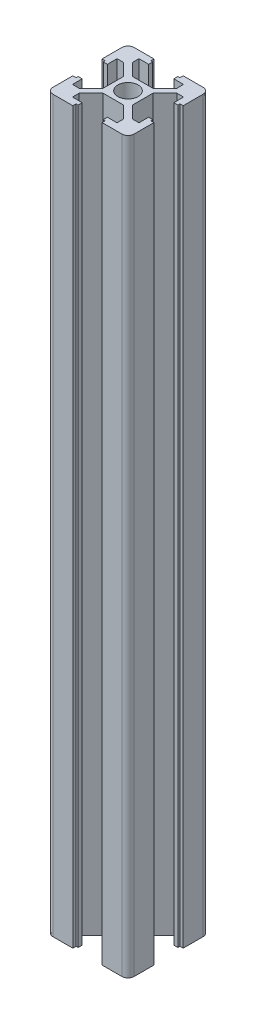
SolidWorks part; units mm, degrees
ref_plane "前视基准面" through (0, 0, 0) normal (0, 0, 1) x (1, 0, 0)
ref_plane "上视基准面" through (0, 0, 0) normal (0, 1, 0) x (1, 0, 0)
ref_plane "右视基准面" through (0, 0, 0) normal (1, 0, 0) x (0, 0, -1)
other "Configuration Table"
sketch "草图1" plane through (0, 0, 0) normal (0, 1, 0) x (1, 0, 0)
  line L0 (-4.4156, 1.3346) -> (-4.4156, 4.4346) construction
  line L1 (-4.4156, 3.874) -> (-4.4156, -1.2047)
  line L2 (1.7237, 4.9346) -> (-3.3549, 4.9346)
  line L3 (2.7844, -1.2047) -> (2.7844, 3.874)
  line L4 (-3.3549, -2.2654) -> (1.7237, -2.2654)
  line L5 (-10.8156, 1.3346) -> (9.1844, 1.3346) construction
  line L6 (-0.8156, 11.3346) -> (-0.8156, -8.6654) construction
  line L7 (-10.8156, 11.3346) -> (-0.8156, 1.3346) construction
  line L8 (-10.8156, 4.9346) -> (-4.4156, 4.9346) construction
  line L9 (-10.0156, 4.4346) -> (-3.9156, 4.4346) construction
  line L10 (-9.0156, 6.8346) -> (-6.3156, 6.8346) construction
  line L11 (-7.3763, 6.8346) -> (-4.4156, 3.874) construction
  line L12 (-10.8156, 9.8346) -> (-10.8156, 4.9346)
  line L13 (-10.8156, 4.9346) -> (-10.0156, 4.9346)
  line L14 (-10.0156, 4.9346) -> (-10.0156, 4.4346)
  line L15 (-10.0156, 4.4346) -> (-9.0156, 4.4346)
  line L16 (-9.0156, 4.4346) -> (-9.0156, 6.8346)
  line L17 (-9.0156, 6.8346) -> (-7.3763, 6.8346)
  line L18 (-7.3763, 6.8346) -> (-4.4156, 3.874)
  line L19 (-3.9156, 10.5346) -> (-3.9156, 9.5346)
  line L20 (-4.4156, 10.5346) -> (-3.9156, 10.5346)
  line L21 (-4.4156, 11.3346) -> (-4.4156, 10.5346)
  line L22 (-9.3156, 11.3346) -> (-4.4156, 11.3346)
  line L23 (-3.9156, 9.5346) -> (-6.3156, 9.5346)
  line L24 (-6.3156, 9.5346) -> (-6.3156, 7.8953)
  line L25 (-6.3156, 7.8953) -> (-3.3549, 4.9346)
  line L26 (9.1844, 11.3346) -> (-0.8156, 1.3346) construction
  line L27 (4.6844, 7.8953) -> (1.7237, 4.9346)
  line L28 (4.6844, 9.5346) -> (4.6844, 7.8953)
  line L29 (2.2844, 9.5346) -> (4.6844, 9.5346)
  line L30 (2.2844, 10.5346) -> (2.2844, 9.5346)
  line L31 (2.7844, 10.5346) -> (2.2844, 10.5346)
  line L32 (2.7844, 11.3346) -> (2.7844, 10.5346)
  line L33 (7.6844, 11.3346) -> (2.7844, 11.3346)
  line L34 (9.1844, 9.8346) -> (9.1844, 4.9346)
  line L35 (9.1844, 4.9346) -> (8.3844, 4.9346)
  line L36 (8.3844, 4.9346) -> (8.3844, 4.4346)
  line L37 (8.3844, 4.4346) -> (7.3844, 4.4346)
  line L38 (7.3844, 4.4346) -> (7.3844, 6.8346)
  line L39 (7.3844, 6.8346) -> (5.7451, 6.8346)
  line L40 (5.7451, 6.8346) -> (2.7844, 3.874)
  line L41 (9.1844, -8.6654) -> (-0.8156, 1.3346) construction
  line L42 (5.7451, -4.1654) -> (2.7844, -1.2047)
  line L43 (7.3844, -4.1654) -> (5.7451, -4.1654)
  line L44 (7.3844, -1.7654) -> (7.3844, -4.1654)
  line L45 (8.3844, -1.7654) -> (7.3844, -1.7654)
  line L46 (8.3844, -2.2654) -> (8.3844, -1.7654)
  line L47 (9.1844, -2.2654) -> (8.3844, -2.2654)
  line L48 (9.1844, -7.1654) -> (9.1844, -2.2654)
  line L49 (7.6844, -8.6654) -> (2.7844, -8.6654)
  line L50 (2.7844, -8.6654) -> (2.7844, -7.8654)
  line L51 (2.7844, -7.8654) -> (2.2844, -7.8654)
  line L52 (2.2844, -7.8654) -> (2.2844, -6.8654)
  line L53 (2.2844, -6.8654) -> (4.6844, -6.8654)
  line L54 (4.6844, -6.8654) -> (4.6844, -5.226)
  line L55 (4.6844, -5.226) -> (1.7237, -2.2654)
  line L56 (-10.8156, -8.6654) -> (-0.8156, 1.3346) construction
  line L57 (-6.3156, -5.226) -> (-3.3549, -2.2654)
  line L58 (-6.3156, -6.8654) -> (-6.3156, -5.226)
  line L59 (-3.9156, -6.8654) -> (-6.3156, -6.8654)
  line L60 (-3.9156, -7.8654) -> (-3.9156, -6.8654)
  line L61 (-4.4156, -7.8654) -> (-3.9156, -7.8654)
  line L62 (-4.4156, -8.6654) -> (-4.4156, -7.8654)
  line L63 (-9.3156, -8.6654) -> (-4.4156, -8.6654)
  line L64 (-10.8156, -7.1654) -> (-10.8156, -2.2654)
  line L65 (-10.8156, -2.2654) -> (-10.0156, -2.2654)
  line L66 (-10.0156, -2.2654) -> (-10.0156, -1.7654)
  line L67 (-10.0156, -1.7654) -> (-9.0156, -1.7654)
  line L68 (-9.0156, -1.7654) -> (-9.0156, -4.1654)
  line L69 (-9.0156, -4.1654) -> (-7.3763, -4.1654)
  line L70 (-7.3763, -4.1654) -> (-4.4156, -1.2047)
  arc A0 (-10.8156, 9.8346) -> (-9.3156, 11.3346) centre (-9.3156, 9.8346) cw
  circle A1 centre (-0.8156, 1.3346) radius 2.5
  arc A2 (7.6844, 11.3346) -> (9.1844, 9.8346) centre (7.6844, 9.8346) cw
  arc A3 (9.1844, -7.1654) -> (7.6844, -8.6654) centre (7.6844, -7.1654) cw
  arc A4 (-9.3156, -8.6654) -> (-10.8156, -7.1654) centre (-9.3156, -7.1654) cw
  point P13 (-0.8156, 1.3346)
  point P84 (-0.8156, 1.3346)
  dimension "D8" = 1.5
  dimension "D9" = 5
  dimension "D1" = 20
  dimension "D2" = 6.2
  dimension "D3" = 7.2
  dimension "D4" = 11
  dimension "D5" = 1.5
  dimension "D6" = 0.8
  dimension "D7" = 1.8
  dimension "D10" = 7.2
extrude "凸台-拉伸1" add sketch "草图1" along normal blind 180
